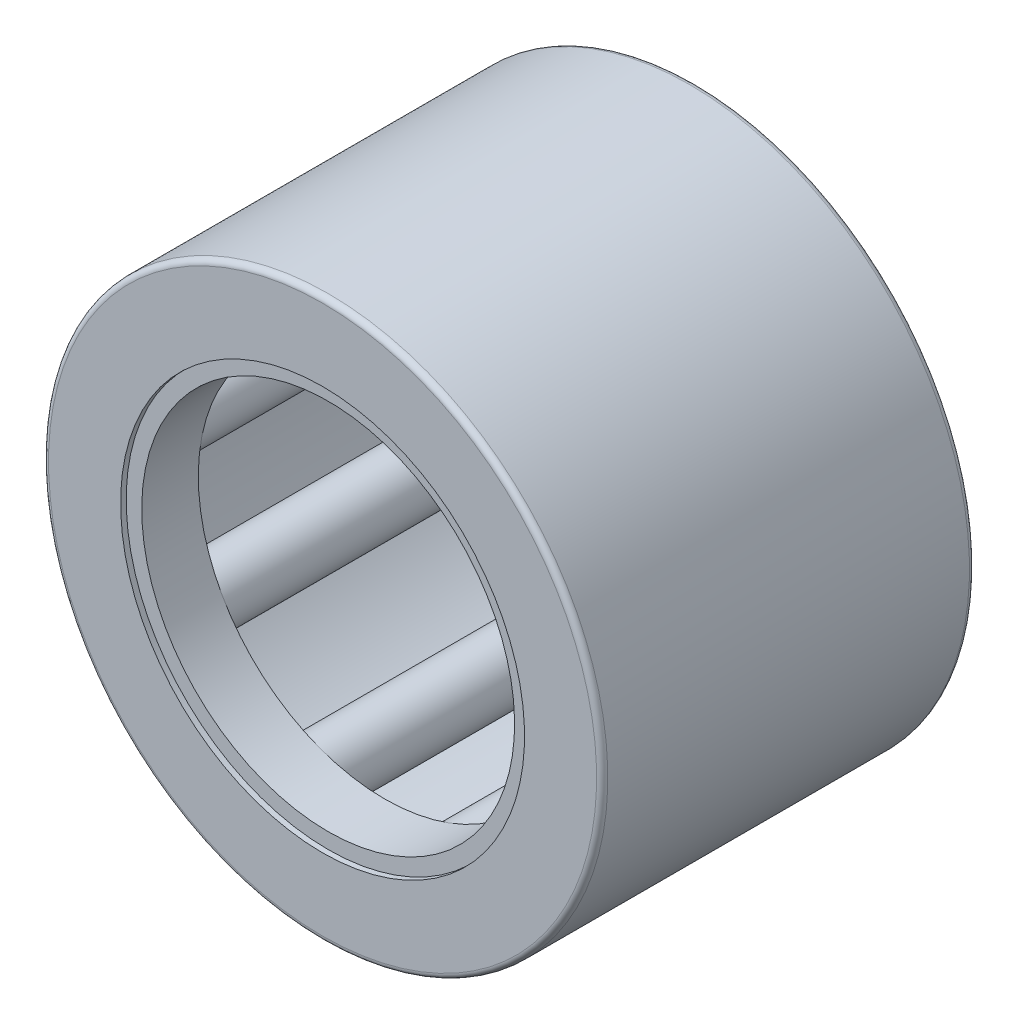
SolidWorks part; units mm, degrees
ref_plane "Front Plane" through (0, 0, 0) normal (0, 0, 1) x (1, 0, 0)
ref_plane "Top Plane" through (0, 0, 0) normal (0, 1, 0) x (1, 0, 0)
ref_plane "Right Plane" through (0, 0, 0) normal (1, 0, 0) x (0, 0, -1)
sketch "Sketch1" plane through (0, 0, 0) normal (1, 0, 0) x (0, 0, -1)
  line L0 (-4, 0) -> (4, 0) construction
  line L1 (0, 0) -> (0, 6) construction
  line L2 (-4, 0) -> (-4, 6) construction
  line L3 (-4, 6) -> (4, 6)
  line L4 (4, 6) -> (4, 0) construction
  line L5 (4, 0) -> (3.3333, 0) construction
  line L6 (3.3333, 0) -> (3.3333, 5.3333) construction
  line L7 (3.3333, 5.3333) -> (-3.3333, 5.3333)
  line L8 (-3.3333, 5.3333) -> (-3.3333, 0) construction
  line L9 (-3.3333, 0) -> (-4, 0) construction
  line L10 (-4, 6) -> (-4, 4.3333)
  line L11 (-4, 4.3333) -> (-3.3333, 4.3333)
  line L12 (-3.3333, 4.3333) -> (-3.3333, 5.3333)
  line L13 (3.3333, 6) -> (3.3333, 5.3333) construction
  line L14 (3.3333, 5.3333) -> (3.3333, 4.3333)
  line L15 (3.3333, 4.3333) -> (4, 4.3333)
  line L16 (4, 4.3333) -> (4, 6)
  line L17 (3.3333, 5.3333) -> (3.3333, 4.6667) construction
  line L18 (3.3333, 4.6667) -> (3.3333, 4) construction
  line L19 (3.3333, -5.3333) -> (3.3333, -4.6667) construction
  line L20 (3.3333, -6) -> (3.3333, -5.3333) construction
  line L21 (4, -4.3333) -> (4, -6) construction
  line L22 (3.3333, -4.3333) -> (4, -4.3333) construction
  line L23 (3.3333, -5.3333) -> (3.3333, -4.3333) construction
  line L24 (-3.3333, -4.3333) -> (-3.3333, -5.3333) construction
  line L25 (-4, -4.3333) -> (-3.3333, -4.3333) construction
  line L26 (-4, -6) -> (-4, -4.3333) construction
  line L27 (3.3333, -5.3333) -> (-3.3333, -5.3333) construction
  line L28 (-4, -6) -> (4, -6) construction
  point P4 (0, 4)
  dimension "C | Width" = 8
  dimension "Fw | ID" = 8
  dimension "D | OD" = 12
sketch "Sketch7" plane through (0, 0, 0) normal (1, 0, 0) x (0, 0, -1)
  line L0 (-4, 6) -> (-4, 4.3333) construction
  line L1 (-4, 4.3333) -> (-3.3333, 4.3333) construction
  line L2 (-3.3333, 4.3333) -> (-3.3333, 5.3333) construction
  line L3 (3.3333, 5.3333) -> (-3.3333, 5.3333) construction
  line L4 (3.3333, 5.3333) -> (3.3333, 4.3333) construction
  line L5 (3.3333, 4.3333) -> (4, 4.3333) construction
  line L6 (4, 4.3333) -> (4, 6) construction
  line L8 (-4, 6) -> (4, 6) construction
  line L9 (-4, 6) -> (-4, 4.3333)
  line L10 (-4, 4.3333) -> (-3.3333, 4.3333)
  line L13 (-3.3333, 4.3333) -> (-3.3333, 5.3333)
  line L16 (3.3333, 5.3333) -> (-3.3333, 5.3333)
  line L17 (3.3333, 5.3333) -> (3.3333, 4.3333)
  line L18 (3.3333, 4.3333) -> (4, 4.3333)
  line L19 (4, 4.3333) -> (4, 6)
  line L20 (-4, 6) -> (4, 6)
revolve "Revolve1" add sketch "Sketch7" angle 360 about L0
sketch "Sketch2" plane through (0, 0, 0) normal (1, 0, 0) x (0, 0, -1)
  line L0 (-4, 4.3333) -> (-3.3333, 4.3333) construction
  line L1 (-2.6667, 4.6667) -> (2.6667, 4.6667) construction
  line L2 (-2.6667, 4.6667) -> (-2.6667, 5.3333) construction
  line L3 (-2.6667, 5.3333) -> (2.6667, 5.3333)
  line L4 (2.6667, 4.6667) -> (2.6667, 5.3333) construction
  line L5 (3.3333, 4.3333) -> (4, 4.3333) construction
  line L6 (-3.3333, 4.6667) -> (-2.6667, 4.6667) construction
  line L7 (2.6667, 4.6667) -> (3.3333, 4.6667) construction
  line L8 (4, 6) -> (4, 0) construction
  line L9 (-2.6667, 4.8333) -> (-2.6667, 4.5) construction
  line L10 (-3.3333, 4.6667) -> (-3.3333, 4.3333) construction
  line L11 (-2.6667, 5.3333) -> (-2.6667, 4.8333)
  line L12 (2.6667, 5.3333) -> (2.6667, 4.8333)
  line L13 (2.6667, 4.8333) -> (-2.6667, 4.8333)
  line L14 (0, 5.3333) -> (0, 4) construction
  line L16 (-2.6667, 4.5) -> (-3.3333, 4.5) construction
  line L17 (0, 0) -> (4, 0) construction
  line L18 (-2.6667, -4.5) -> (-3.3333, -4.5) construction
  line L19 (0, -5.3333) -> (0, -4) construction
  line L20 (-3.3333, -4.6667) -> (-3.3333, -4.3333) construction
  line L21 (-2.6667, -4.8333) -> (-2.6667, -4.5) construction
  line L22 (2.6667, -4.6667) -> (3.3333, -4.6667) construction
  line L23 (-3.3333, -4.6667) -> (-2.6667, -4.6667) construction
  line L24 (2.6667, -4.6667) -> (2.6667, -5.3333) construction
  line L25 (-2.6667, -4.6667) -> (-2.6667, -5.3333) construction
  line L26 (-2.6667, -4.6667) -> (2.6667, -4.6667) construction
  line L27 (2.6667, -4.8333) -> (-2.6667, -4.8333) construction
  line L28 (2.6667, -5.3333) -> (2.6667, -4.8333) construction
  line L29 (-2.6667, -5.3333) -> (-2.6667, -4.8333) construction
  line L30 (-2.6667, -5.3333) -> (2.6667, -5.3333) construction
  line L33 (3.3333, 5.3333) -> (-3.3333, 5.3333) construction
  line L34 (3.3333, 5.3333) -> (3.3333, 4.3333) construction
  line L35 (-3.3333, 4.3333) -> (-3.3333, 5.3333) construction
  line L36 (0, 0) -> (0, 6) construction
  point P16 (0, 4.6667)
revolve "Revolve2" add sketch "Sketch2" angle 360 about L1
sketch "Sketch3" plane through (0, 0, 0) normal (1, 0, 0) x (0, 0, -1)
  line L1 (-3.3333, 4.6667) -> (3.3333, 4.6667)
  line L2 (-3.3333, 4.6667) -> (-3.3333, 4.8333)
  line L3 (-3.3333, 4.8333) -> (3.3333, 4.8333)
  line L4 (3.3333, 4.6667) -> (3.3333, 4.8333)
  line L5 (0, 0) -> (4, 0) construction
  line L7 (3.3333, -4.6667) -> (3.3333, -4.8333) construction
  line L8 (-3.3333, -4.8333) -> (3.3333, -4.8333) construction
  line L9 (-3.3333, -4.6667) -> (-3.3333, -4.8333) construction
  line L10 (-3.3333, -4.6667) -> (3.3333, -4.6667) construction
  line L11 (3.3333, 5.3333) -> (3.3333, 4.3333) construction
  line L12 (4, 6) -> (4, 0) construction
revolve "Revolve3" add sketch "Sketch3" angle 360 about L1
ref_axis "Axis1" through (0, 4.3333, 4) along (0, 1, 0)
pattern_circular "CirPattern1" count 9 every 40 about axis through (0, 0, 4) along (0, 0, -1) of bodies 166 167
fillet "Fillet1" radius 0.12 2 edges at (0, -6, -4) (0, -6, 4)
sketch "Sketch4" plane through (0, 0, 0) normal (1, 0, 0) x (0, 0, -1)
  line L0 (2.6667, 5.3333) -> (2.6667, 4.8333) construction
  line L1 (3.88, 4) -> (2.6667, 4)
  line L2 (3.88, 4) -> (3.88, 4.3333)
  line L3 (3.88, 4.3333) -> (2.6667, 4.3333)
  line L4 (2.6667, 4) -> (2.6667, 4.3333)
  line L7 (3.3333, 4.3333) -> (4, 4.3333) construction
  line L8 (3.88, -6) -> (3.88, 6) construction
revolve "Revolve4" add sketch "Sketch4" angle 360 about L0
sketch "Sketch5" plane through (0, 0, 0) normal (1, 0, 0) x (0, 0, -1)
  line L0 (-3.88, 6) -> (-3.88, -6) construction
  line L1 (-2.6667, 4) -> (-3.88, 4)
  line L2 (-2.6667, 4) -> (-2.6667, 4.3333)
  line L3 (-2.6667, 4.3333) -> (-3.88, 4.3333)
  line L4 (-3.88, 4) -> (-3.88, 4.3333)
  line L5 (-2.6667, 5.3333) -> (-2.6667, 4.8333) construction
  line L6 (-4, 4.3333) -> (-3.3333, 4.3333) construction
revolve "Revolve5" add sketch "Sketch5" angle 360 about L0
sketch "Front View" plane through (0, 0, 0) normal (0, 0, 1) x (1, 0, 0)
  circle A0 centre (0, 0) radius 4 construction
  circle A1 centre (0, 0) radius 6 construction
  dimension "ID" = 8
  dimension "OD" = 12
sketch "Right View" plane through (0, 0, 0) normal (1, 0, 0) x (0, 0, -1)
  line L0 (-4, 6) -> (4, 6) construction
  line L1 (-4, 6) -> (4, 6) construction
  line L2 (0, 0) -> (0, 6) construction
  point P4 (0, 6)
  dimension "Width" = 8
equation "\"Rollers@CirPattern1\"  = \"OD@Sketch1\"*.75"
equation "\"D1@Fillet1\" = \"D | OD@Sketch1\" * .01"
equation "\"Angle@CirPattern1\"=360 / \"Rollers@CirPattern1\""
equation "\"ID@Front View\" = \"Fw | ID@Sketch1\""
equation "\"OD@Front View\" = \"D | OD@Sketch1\""
equation "\"Width@Right View\" = \"C | Width@Sketch1\""
